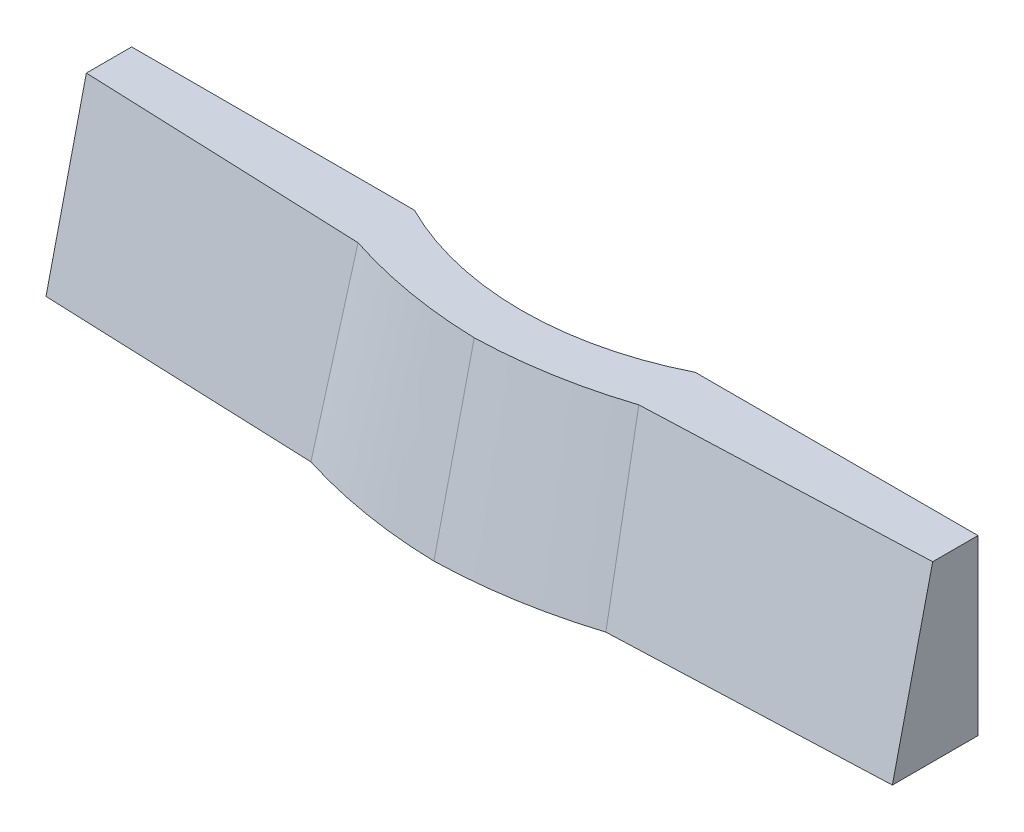
SolidWorks part; units mm, degrees
ref_plane "Front Plane" through (0, 0, 0) normal (0, 0, 1) x (1, 0, 0)
ref_plane "Top Plane" through (0, 0, 0) normal (0, 1, 0) x (1, 0, 0)
ref_plane "Right Plane" through (0, 0, 0) normal (1, 0, 0) x (0, 0, -1)
sketch "Sketch1" plane through (0, 0, 0) normal (0, 1, 0) x (1, 0, 0)
  line L0 (-105, -30) -> (-105, -41.2422) construction
  line L1 (-34.8399, -30) -> (34.8399, -30) construction
  line L2 (105, -30) -> (105, -41.2422) construction
  line L3 (0, -142.6423) -> (0, 36.4059) construction
  line L4 (0, -100) -> (0, 70) construction
  line L5 (-42.9151, -50) -> (42.9151, -50) construction
  line L6 (-105, -41.2422) -> (-34.8399, -43.9889) construction
  line L7 (34.8399, -43.9889) -> (105, -41.2422) construction
  line L8 (-105, -30) -> (-34.8399, -30) construction
  line L9 (105, -30) -> (34.8399, -30) construction
  line L10 (-34.8399, -30) -> (-34.8399, -43.9889) construction
  line L11 (34.8399, -30) -> (34.8399, -43.9889) construction
  arc A0 (-34.8399, -30) -> (34.8399, -30) centre (0, 39.341) ccw construction
  arc A1 (-34.8399, -43.9889) -> (0, -50) centre (3.1802, 72.4023) ccw construction
  arc A2 (34.8399, -43.9889) -> (0, -50) centre (-3.1802, 72.4023) cw construction
  point P14 (0, 0)
  dimension "D1" = 77.6015
  dimension "D2" = 122.4436
  dimension "D3" = 34.8399
  dimension "D4" = 70.1601
  dimension "D5" = 70.1601
  dimension "D6" = 92.242
  dimension "D7" = 13.9889
ref_plane "Plane1" through (0, -25, 0) normal (0, 1, 0) x (1, 0, 0)
sketch "Sketch2" plane through (0, -25, 0) normal (0, 1, 0) x (1, 0, 0)
  line L0 (-105, -30) -> (-105, -51.2498)
  line L1 (105, -30) -> (105, -51.2498)
  line L2 (-105, -30) -> (-34.8399, -30)
  line L3 (34.8399, -30) -> (105, -30)
  line L13 (36.5941, -53.9279) -> (105.3912, -51.2345)
  line L14 (-105.3912, -51.2345) -> (-36.5941, -53.9279)
  line L15 (36.5941, -53.9279) -> (105, -51.2498)
  line L16 (-105, -51.2498) -> (-36.5941, -53.9279)
  arc A0 (-34.8399, -30) -> (34.8399, -30) centre (0, 39.341) ccw
  arc A1 (-34.8399, -30) -> (34.8399, -30) centre (0, 39.341) ccw construction
  arc A10 (0, -60.0031) -> (36.5941, -53.9279) centre (-3.1802, 72.4023) ccw
  arc A11 (-36.5941, -53.9279) -> (0, -60.0031) centre (3.1802, 72.4023) ccw
  arc A12 (0, -60.0031) -> (36.5941, -53.9279) centre (-3.1802, 72.4023) ccw
  arc A13 (-36.5941, -53.9279) -> (0, -60.0031) centre (3.1802, 72.4023) ccw
  dimension "D1" = 10
ref_plane "Plane2" through (0, 18, 0) normal (0, 1, 0) x (1, 0, 0)
sketch "Sketch3" plane through (0, 18, 0) normal (0, 1, 0) x (1, 0, 0)
  line L0 (-105, -30) -> (-34.8399, -30)
  line L1 (-105, -41.2422) -> (-105, -30)
  line L2 (-105, -41.2422) -> (-34.8399, -43.9889)
  line L3 (34.8399, -30) -> (105, -30)
  line L4 (105, -30) -> (105, -41.2422)
  line L5 (105, -41.2422) -> (34.8399, -43.9889)
  line L6 (34.8399, -43.9889) -> (105, -41.2422) construction
  line L7 (0, -42.1686) -> (0, -57.8303) construction
  line L8 (0, -142.6423) -> (0, 36.4059) construction
  line L9 (-105, -41.2422) -> (-34.8399, -43.9889) construction
  arc A0 (-34.8399, -30) -> (34.8399, -30) centre (0, 39.341) ccw
  arc A1 (0, -50) -> (34.8399, -43.9889) centre (-3.1802, 72.4023) ccw
  arc A16 (0, -50) -> (34.8399, -43.9889) centre (-3.1802, 72.4023) ccw construction
  arc A18 (-34.8399, -43.9889) -> (0, -50) centre (3.1802, 72.4023) ccw
  arc A19 (-34.8399, -43.9889) -> (0, -50) centre (3.1802, 72.4023) ccw construction
  arc A20 (-34.8399, -30) -> (34.8399, -30) centre (0, 39.341) ccw construction
loft "Loft2" add profiles "Sketch2", "Sketch3" connector at (-105, -25, 51.2498) connector at (-105, 18, 41.2422)
